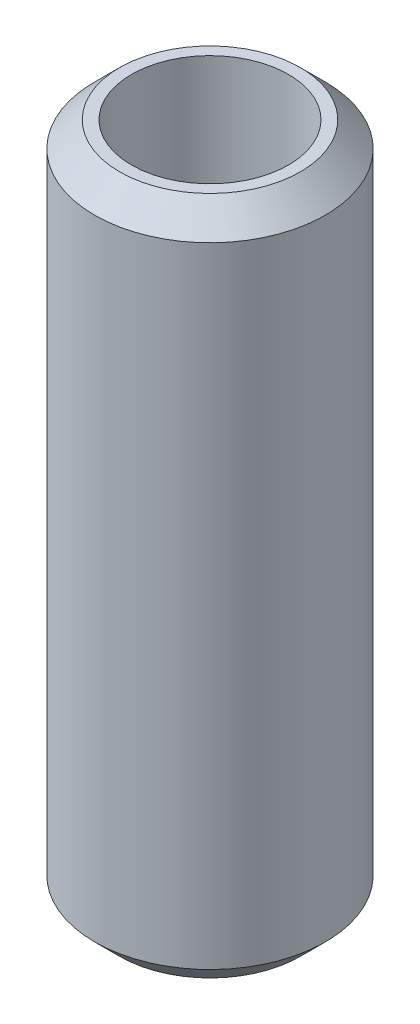
SolidWorks part; units mm, degrees
ref_plane "Front Plane" through (0, 0, 0) normal (0, 0, 1) x (1, 0, 0)
ref_plane "Top Plane" through (0, 0, 0) normal (0, 1, 0) x (1, 0, 0)
ref_plane "Right Plane" through (0, 0, 0) normal (1, 0, 0) x (0, 0, -1)
sketch "Sketch1" plane through (0, 0, 0) normal (0, 1, 0) x (1, 0, 0)
  circle A0 centre (0, 0) radius 25
  dimension "SHAFT_OD" = 50
extrude "Boss-Extrude1" add sketch "Sketch1" along normal blind 147.2227
sketch "Sketch2" plane through (0, 0, 0) normal (0, 1, 0) x (1, 0, 0)
  circle A0 centre (0, 0) radius 17.0145
  dimension "BORE_D" = 34.029
extrude "Cut-Extrude1" cut sketch "Sketch2" along normal through all
chamfer "Chamfer1" distance 5.4194 angle 45 2 edges at (0, 147.2227, 25) (0, 0, 25)
